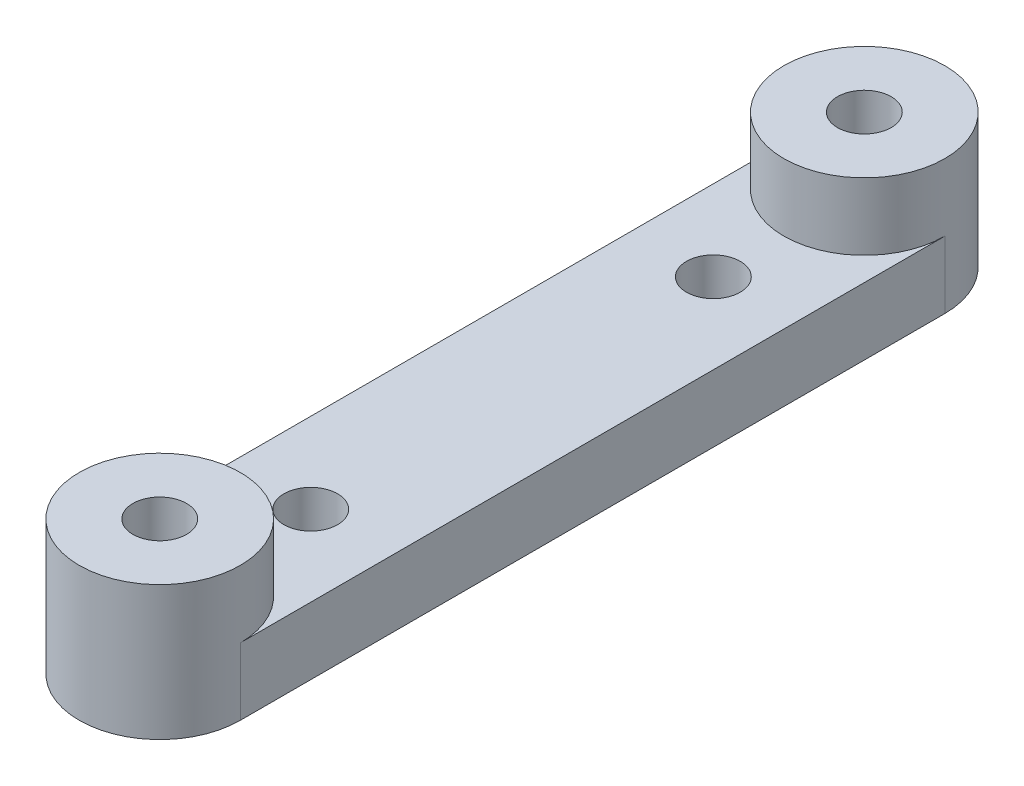
SolidWorks part; units mm, degrees
ref_plane "Front" through (0, 0, 0) normal (0, 0, 1) x (1, 0, 0)
ref_plane "Top" through (0, 0, 0) normal (0, 1, 0) x (1, 0, 0)
ref_plane "Right" through (0, 0, 0) normal (1, 0, 0) x (0, 0, -1)
sketch "Sketch1" plane through (0, 0, 0) normal (0, 1, 0) x (1, 0, 0)
  line L1 (-6, -32.25) -> (6, -32.25)
  line L2 (-6, -32.25) -> (-6, 32.25)
  line L3 (-6, 32.25) -> (6, 32.25)
  line L4 (6, -32.25) -> (6, 32.25)
  line L5 (-6, -32.25) -> (6, 32.25) construction
  line L6 (-6, 32.25) -> (6, -32.25) construction
  point P0 (0, 0)
  dimension "D1" = 64.5
  dimension "D2" = 12
extrude "Boss-Extrude1" add sketch "Sketch1" along normal blind 5
fillet "Fillet1" radius 6 4 edges at (-6, 2.5, -32.25) (6, 2.5, -32.25) (-6, 2.5, 32.25) (6, 2.5, 32.25)
sketch "Sketch2" plane through (0, 5, 0) normal (0, 1, 0) x (1, 0, 0)
  line L0 (0, 0) -> (-11.0095, 0) construction
  line L1 (0, 0) -> (0, -10.2979) construction
  circle A0 centre (0, -26.25) radius 2
  circle A1 centre (0, 26.25) radius 2
  dimension "D2" = 4
  dimension "D1" = 52.5
extrude "Cut-Extrude1" cut sketch "Sketch2" against normal through all
sketch "Sketch3" plane through (0, 5, 0) normal (0, 1, 0) x (1, 0, 0)
  line L1 (-6, 26.25) -> (-6, -26.25) construction
  circle A0 centre (0, -26.25) radius 6
  circle A1 centre (0, 26.25) radius 6
  circle A2 centre (0, 26.25) radius 2
  circle A3 centre (0, -26.25) radius 2
  circle A4 centre (0, -26.25) radius 2 construction
  circle A5 centre (0, 26.25) radius 2 construction
extrude "Boss-Extrude2" add sketch "Sketch3" along normal blind 5
sketch "Sketch4" plane through (0, 5, 0) normal (0, 1, 0) x (1, 0, 0)
  line L0 (0, 0) -> (0, 6.5632) construction
  line L1 (0, 0) -> (13.3026, 0) construction
  circle A0 centre (0, 15) radius 2
  circle A1 centre (0, -15) radius 2
  dimension "D1" = 4
  dimension "D2" = 15
extrude "Cut-Extrude2" cut sketch "Sketch4" against normal through all
sketch "Sketch5" plane through (0, 0, 0) normal (0, -1, 0) x (1, 0, 0)
  line L0 (0, 0) -> (0, 44.5) construction
  line L1 (4.6188, 26.25) -> (2.3094, 30.25)
  line L2 (2.3094, 30.25) -> (-2.3094, 30.25)
  line L3 (-2.3094, 30.25) -> (-4.6188, 26.25)
  line L4 (-4.6188, 26.25) -> (-2.3094, 22.25)
  line L5 (-2.3094, 22.25) -> (2.3094, 22.25)
  line L6 (2.3094, 22.25) -> (4.6188, 26.25)
  line L7 (2.3094, -22.25) -> (-2.3094, -22.25)
  line L8 (-2.3094, -22.25) -> (-4.6188, -26.25)
  line L9 (-4.6188, -26.25) -> (-2.3094, -30.25)
  line L10 (-2.3094, -30.25) -> (2.3094, -30.25)
  line L11 (2.3094, -30.25) -> (4.6188, -26.25)
  line L12 (4.6188, -26.25) -> (2.3094, -22.25)
  circle A0 centre (0, 26.25) radius 4 construction
  circle A1 centre (0, -26.25) radius 4 construction
  point P10 (0, -30.25)
  point P23 (0, 22.25)
  dimension "D1" = 8
extrude "Cut-Extrude3" cut sketch "Sketch5" against normal blind 2.5
